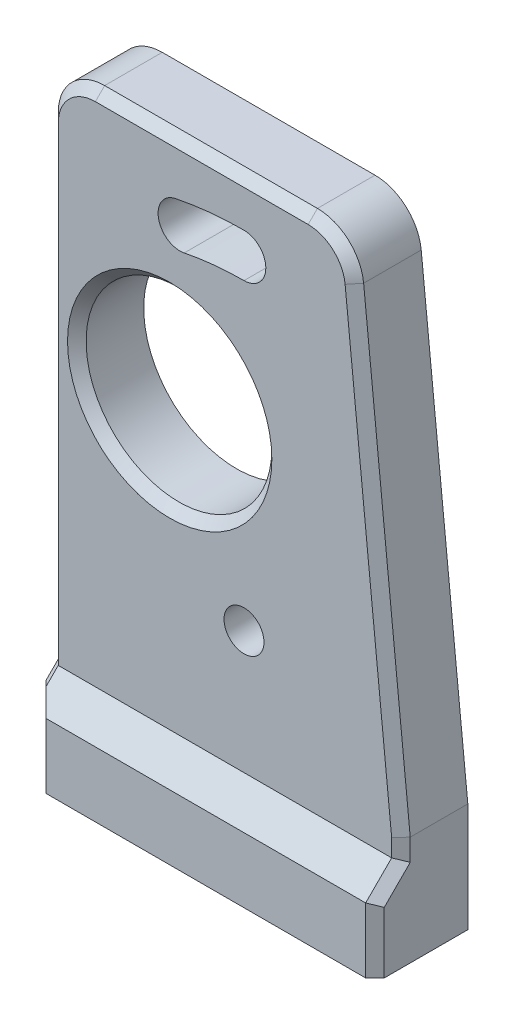
SolidWorks part; units mm, degrees
ref_plane "Ebene vorne" through (0, 0, 0) normal (0, 0, 1) x (1, 0, 0)
ref_plane "Ebene oben" through (0, 0, 0) normal (0, 1, 0) x (1, 0, 0)
ref_plane "Ebene rechts" through (0, 0, 0) normal (1, 0, 0) x (0, 0, -1)
sketch "Skizze1" plane through (0, 0, 0) normal (0, 0, 1) x (1, 0, 0)
  line L0 (0, 0) -> (71.8499, 0) construction
  line L1 (3.5487, 35) -> (89.7998, -6) construction
  line L2 (10.7739, 31.5654) -> (18.287, 47.3706) construction
  line L3 (6.9832, 42.2252) -> (14.1827, 57.3706) construction
  line L4 (14.1827, 57.3706) -> (28.287, 57.3706) construction
  line L5 (28.287, 57.3706) -> (28.287, 0)
  line L6 (28.287, 0) -> (-13.0888, 0)
  line L7 (6.9832, 42.2252) -> (0.1141, 27.7748) construction
  line L8 (0.1141, 27.7748) -> (-13.0888, 0) construction
  line L9 (-13.0888, 0) -> (-13.0888, 27.3482)
  line L10 (-13.0888, 57.3706) -> (14.1827, 57.3706) construction
  line L11 (3.5487, 35) -> (-13.0888, 42.9087) construction
  line L12 (-8.0888, 57.3706) -> (-8.0888, 15.7603) construction
  line L13 (-8.0888, 40.5319) -> (-29.0289, 40.5319) construction
  line L14 (-13.0888, 57.3706) -> (-13.0888, 65.3706)
  line L15 (-13.0888, 65.3706) -> (28.287, 65.3706)
  line L16 (28.287, 65.3706) -> (28.287, 57.3706)
  line L17 (-13.0888, 53.7156) -> (-13.0888, 27.3482)
  line L18 (-13.0888, 53.7156) -> (-13.0888, 57.3706)
  arc A0 (0, 0) -> (84.5911, 83.8491) centre (89.7998, -6) cw construction
  circle A1 centre (3.5487, 35) radius 5.5 construction
  circle A2 centre (3.5487, 35) radius 2.5 construction
  circle A3 centre (18.287, 47.3706) radius 2.25 construction
  circle A4 centre (3.2608, 15.7603) radius 2.25 construction
  arc A5 (0.1141, 27.7748) -> (6.9832, 42.2252) centre (3.5487, 35) ccw construction
  circle A7 centre (-8.0888, 23.0319) radius 2.1 construction
  circle A8 centre (-8.0888, 58.0319) radius 2.1 construction
  dimension "D1" = 90
  dimension "D2" = 11
  dimension "D3" = 5
  dimension "D4" = 35
  dimension "D6" = 4.5
  dimension "D12" = 4.2
  dimension "D5" = 8
  dimension "D7" = 35
  dimension "D8" = 10
  dimension "D9" = 10
  dimension "D10" = 6
  dimension "D13" = 35
  dimension "D14" = 5
  dimension "D15" = 8
extrude "Aufsatz-Linear austragen1" add sketch "Skizze1" along normal blind 10
sketch "Skizze2" plane through (0, 0, 0) normal (0, -1, 0) x (1, 0, 0)
  line L0 (-13.0888, 5) -> (28.287, 5) construction
  line L2 (28.287, 10) -> (28.287, 0) construction
  line L3 (7.5991, 5) -> (7.5991, 10) construction
  line L4 (-13.0888, 10) -> (28.287, 10) construction
  line L5 (0, 0) -> (0, 10) construction
  circle A0 centre (-7, 5) radius 1.5
  circle A2 centre (6.18, 5) radius 1.5
  circle A3 centre (19.36, 5) radius 1.5
  dimension "D1" = 3
  dimension "D2" = 7
  dimension "D3" = 6.18
  dimension "D4" = 13.18
extrude "Schnitt-Linear austragen1" cut sketch "Skizze2" against normal blind 8
sketch "Skizze4" plane through (0, 0, 10) normal (0, 0, 1) x (1, 0, 0)
  line L0 (-15.0952, 10) -> (28.287, 10)
  line L2 (28.287, 0) -> (28.287, 65.3706) construction
  line L3 (28.287, 10) -> (36.0933, 46.99)
  line L4 (36.0933, 46.99) -> (30.4291, 65.9575)
  line L5 (30.4291, 65.9575) -> (-16.081, 65.9575)
  line L6 (-16.081, 65.9575) -> (-16.081, 27.7535)
  line L7 (-16.081, 27.7535) -> (-15.0952, 10)
  line L8 (-13.0888, 0) -> (28.287, 0) construction
  dimension "D1" = 10
extrude "Schnitt-Linear austragen3" cut sketch "Skizze4" against normal blind 2.8
sketch "Skizze7" plane through (0, 0, 7.2) normal (0, 0, 1) x (1, 0, 0)
  line L0 (-8.0888, 58.0319) -> (-8.0888, 23.0319) construction
  line L1 (-8.0888, 40.5319) -> (-0.0888, 40.5319) construction
  circle A0 centre (-0.0888, 40.5319) radius 10
  point P7 (0, 0)
  point P8 (0, 0)
  dimension "D2" = 20
  dimension "D1" = 8
extrude "Schnitt-Linear austragen5" cut sketch "Skizze7" against normal through all and the other way through all
chamfer "Fase1" distance 3 angle 45 1 edges at (7.5991, 10, 10)
sketch "Skizze5" plane through (0, 0, 0) normal (0, 0, -1) x (-1, 0, 0)
  line L0 (-24.8127, 11.7368) -> (-19.336, 65.3706)
  line L1 (-28.287, 65.3706) -> (13.0888, 65.3706) construction
  line L2 (-19.336, 65.3706) -> (-28.287, 65.3706)
  line L3 (-28.287, 65.3706) -> (-28.287, 0)
  line L4 (-24.8127, 11.7368) -> (-24.8127, 0)
  line L5 (13.0888, 0) -> (-28.287, 0) construction
  line L6 (-24.8127, 0) -> (-28.287, 0)
extrude "Schnitt-Linear austragen4" cut sketch "Skizze5" against normal blind 10
fillet "Verrundung1" radius 5 2 edges at (-13.0888, 65.3706, 3.6) (19.336, 65.3706, 3.6)
chamfer "Fase2" distance 1 angle 45 10 edges at (22.3037, 36.3077, 7.2) (-13.0888, 35.0853, 7.2) (18.1717, 64.0814, 7.2) (-11.6243, 63.9062, 7.2) (3.3659, 65.3706, 7.2) (-13.0888, 8.4, 8.6) (24.8127, 10.7684, 7.2) (24.8127, 3.5, 10) (24.8127, 8.4, 8.6) (9.9112, 40.5319, 7.2)
chamfer "Fase3" distance 2.5 angle 45 1 edges at (-13.0888, 2.7929, 10)
sketch "Skizze8" [suppressed] plane through (0, 0, 0) normal (0, 0, -1) x (-1, 0, 0)
  circle A0 centre (8.0888, 23.0319) radius 3.6
  dimension "D1" = 7.2
extrude "Schnitt-Linear austragen6" [suppressed] cut sketch "Skizze8" against normal blind 3
sketch "Skizze9" plane through (0, 0, 7.2) normal (0, 0, 1) x (1, 0, 0)
  line L0 (-0.0888, 40.5319) -> (-0.0888, 57.3244) construction
  line L1 (-0.0888, 40.5319) -> (25.9259, 40.5319) construction
  line L2 (7.9112, 23.0319) -> (7.9112, 58.0319) construction
  circle A0 centre (7.9112, 58.0319) radius 2.15
  circle A1 centre (7.9112, 23.0319) radius 2.15
  point P7 (7.9112, 40.5319)
  dimension "D3" = 4.3
  dimension "D1" = 35
  dimension "D2" = 8
extrude "Schnitt-Linear austragen7" cut sketch "Skizze9" against normal through all
sketch "Skizze10" plane through (0, 0, 0) normal (0, 0, -1) x (-1, 0, 0)
  circle A0 centre (-7.9112, 23.0319) radius 3.65
  dimension "D1" = 7.3
extrude "Schnitt-Linear austragen8" cut sketch "Skizze10" against normal blind 2.5
chamfer "Fase4" distance 1.5 angle 45 1 edges at (5.7612, 23.0319, 2.5)
sketch "Skizze11" plane through (0, 0, 7.2) normal (0, 0, 1) x (1, 0, 0)
  arc A0 (7.9112, 58.0319) -> (1.01, 57.3448) centre (7.9112, 23.0319) ccw construction
  arc A1 (7.9112, 60.3819) -> (0.5466, 59.6487) centre (7.9112, 23.0319) ccw
  arc A2 (7.9112, 55.6819) -> (1.4734, 55.041) centre (7.9112, 23.0319) ccw
  arc A3 (7.9112, 55.6819) -> (7.9112, 60.3819) centre (7.9112, 58.0319) ccw
  arc A4 (0.5466, 59.6487) -> (1.4734, 55.041) centre (1.01, 57.3448) ccw
  circle A8 centre (7.9112, 58.0319) radius 2.15 construction
  point P5 (4.4435, 57.8597)
  point P12 (1.01, 57.3448)
  dimension "D1" = 0.2
extrude "Schnitt-Linear austragen9" cut sketch "Skizze11" against normal blind 10
